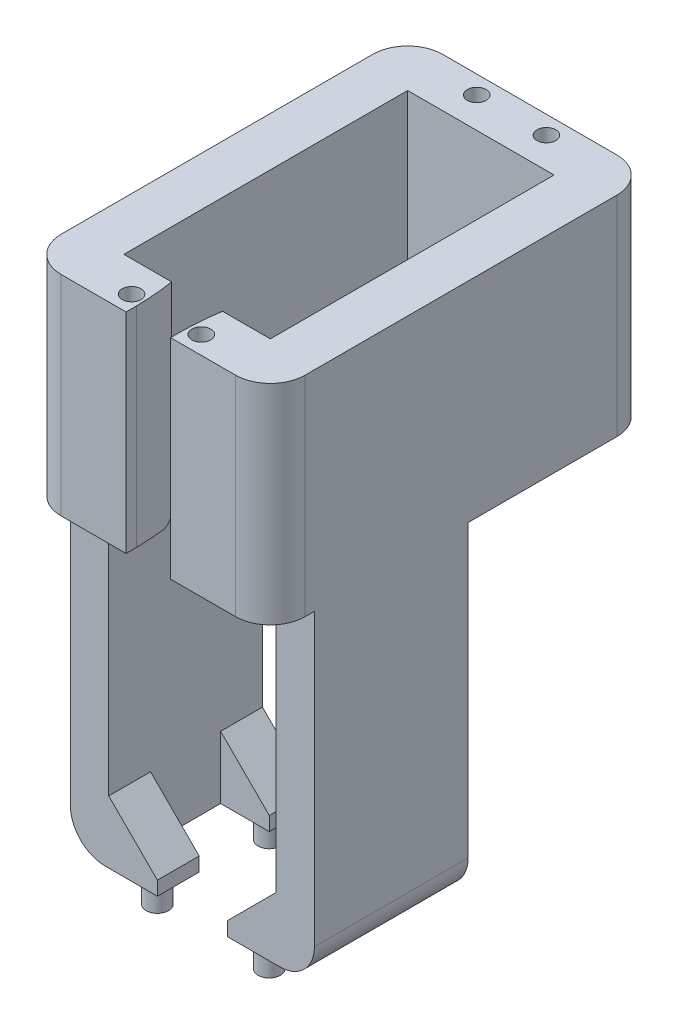
SolidWorks part; units mm, degrees
ref_plane "Front Plane" through (0, 0, 0) normal (0, 0, 1) x (1, 0, 0)
ref_plane "Top Plane" through (0, 0, 0) normal (0, 1, 0) x (1, 0, 0)
ref_plane "Right Plane" through (0, 0, 0) normal (1, 0, 0) x (0, 0, -1)
sketch "Sketch2" plane through (0, 0, 0) normal (0, 1, 0) x (1, 0, 0)
  line L0 (-17.5, 27.35) -> (-17.5, -27.35)
  line L1 (-10.5, 20.35) -> (10.5, 20.35)
  line L2 (-10.5, 20.35) -> (-10.5, -20.35)
  line L3 (-10.5, -20.35) -> (10.5, -20.35)
  line L4 (10.5, 20.35) -> (10.5, -20.35)
  line L5 (-10.5, 20.35) -> (10.5, -20.35) construction
  line L6 (-10.5, -20.35) -> (10.5, 20.35) construction
  line L7 (-17.5, -27.35) -> (17.5, -27.35)
  line L8 (17.5, 27.35) -> (17.5, -27.35)
  line L9 (-17.5, 27.35) -> (17.5, 27.35)
  line L10 (0, 20.35) -> (0, -20.35) construction
  line L11 (-10.5, 0) -> (10.5, 0) construction
  circle A0 centre (-5, 24.75) radius 1.35
  circle A1 centre (5, 24.75) radius 1.35
  circle A2 centre (-5, -24.75) radius 1.35
  circle A3 centre (5, -24.75) radius 1.35
  point P0 (0, 0)
  dimension "D7" = 2.7
  dimension "D8" = 24.75
  dimension "D9" = 5
  dimension "D1" = 21
  dimension "D2" = 40.7
  dimension "D3" = 7
  dimension "D4" = 7
  dimension "D5" = 7
  dimension "D6" = 7
extrude "Boss-Extrude1" add sketch "Sketch2" against normal blind 30
sketch "Sketch4" plane through (0, 0, 0) normal (0, 1, 0) x (1, 0, 0)
  line L0 (-3.25, -21.85) -> (-3.05, -21.85) construction
  line L1 (-10.5, -20.35) -> (10.5, -20.35) construction
  line L2 (-3.25, -20.35) -> (-3.25, -21.85) construction
  line L3 (-3, -25.85) -> (3, -25.85) construction
  line L4 (3.25, -20.35) -> (-3.25, -20.35) construction
  line L5 (-3.05, -21.85) -> (-3, -25.85) construction
  line L6 (0, -20.35) -> (0, -25.85) construction
  line L7 (3.25, -20.35) -> (3.25, -21.85) construction
  line L8 (3.25, -21.85) -> (3.05, -21.85) construction
  line L9 (3.05, -21.85) -> (3, -25.85) construction
  line L10 (-3, -25.85) -> (-2.25, -25.85) construction
  line L11 (-2.25, -25.85) -> (-2.25, -27.35) construction
  line L12 (-17.5, -27.35) -> (17.5, -27.35) construction
  line L13 (-2.25, -27.35) -> (2.25, -27.35) construction
  line L14 (2.25, -27.35) -> (2.25, -25.85) construction
  line L15 (2.25, -25.85) -> (3, -25.85) construction
  line L16 (-3.25, -21.8525) -> (-3.2, -25.8525) construction
  line L17 (-3.45, -20.35) -> (-3.45, -21.85) construction
  line L18 (-3.2, -25.8525) -> (-3.1813, -27.35)
  line L19 (-3.6478, -20.35) -> (3.6478, -20.35)
  line L20 (3.1813, -27.35) -> (-3.1813, -27.35)
  line L21 (3.2, -25.8525) -> (3.1813, -27.35)
  arc A0 (-3.2, -25.8525) -> (-3.6478, -20.35) centre (-43.4094, -26.3551) ccw
  arc A1 (3.2, -25.8525) -> (3.6478, -20.35) centre (43.4094, -26.3551) cw
  point P11 (0, -20.35)
  dimension "D1" = 6.5
  dimension "D2" = 1.5
  dimension "D3" = 6
  dimension "D4" = 4.5
  dimension "D5" = 4
  dimension "D6" = 6.1
  dimension "D7" = 0.2
extrude "Cut-Extrude2" cut sketch "Sketch4" against normal up to next
fillet "Bordes_Servo" radius 1.5 5 edges at (0, -30, -20.35) (-7.0739, -30, 20.35) (7.0739, -30, 20.35) (-10.5, -30, 0) (10.5, -30, 0)
sketch "Sketch5" plane through (0, -30, 0) normal (0, -1, 0) x (1, 0, 0)
  line L0 (-3.6478, 20.35) -> (-10.5, 20.35) construction
  line L1 (-17.5, -27.35) -> (-17.5, 27.35) construction
  line L2 (-8.025, 1.975) -> (8.025, 1.975) construction
  line L3 (-8.025, 1.975) -> (-8.025, 18.025) construction
  line L4 (-8.025, 18.025) -> (8.025, 18.025) construction
  line L5 (8.025, 1.975) -> (8.025, 18.025) construction
  line L6 (-8.025, 1.975) -> (8.025, 18.025) construction
  line L7 (-8.025, 18.025) -> (8.025, 1.975) construction
  line L12 (-17.5, 21.025) -> (-12, 21.025)
  line L13 (-17.5, 21.025) -> (-17.5, -1.025)
  line L14 (-17.5, -1.025) -> (-12, -1.025)
  line L15 (-12, 21.025) -> (-12, -1.025)
  line L16 (-12, -21.85) -> (-12, 21.85) construction
  line L17 (0, 18.025) -> (0, 1.975) construction
  line L18 (-12, 21.025) -> (-5.025, 21.025)
  line L19 (-12, 21.025) -> (-12, 15.025)
  line L20 (-12, 15.025) -> (-5.025, 15.025)
  line L21 (-5.025, 21.025) -> (-5.025, 15.025)
  line L22 (-8.025, 10) -> (8.025, 10) construction
  line L23 (-5.025, -1.025) -> (-5.025, 4.975)
  line L24 (-12, 4.975) -> (-5.025, 4.975)
  line L25 (-12, -1.025) -> (-12, 4.975)
  line L26 (-12, -1.025) -> (-5.025, -1.025)
  line L27 (8.025, 1.975) -> (8.025, 18.025) construction
  line L28 (12, -1.025) -> (5.025, -1.025)
  line L29 (12, -1.025) -> (12, 4.975)
  line L30 (12, 4.975) -> (5.025, 4.975)
  line L31 (5.025, -1.025) -> (5.025, 4.975)
  line L32 (5.025, 21.025) -> (5.025, 15.025)
  line L33 (12, 15.025) -> (5.025, 15.025)
  line L34 (12, 21.025) -> (12, 15.025)
  line L35 (12, 21.025) -> (5.025, 21.025)
  line L36 (12, 21.025) -> (12, -1.025)
  line L37 (17.5, -1.025) -> (12, -1.025)
  line L38 (17.5, 21.025) -> (17.5, -1.025)
  line L39 (17.5, 21.025) -> (12, 21.025)
  circle A0 centre (8.025, 1.975) radius 1.6
  circle A1 centre (-8.025, 1.975) radius 1.6
  circle A2 centre (-8.025, 18.025) radius 1.6
  circle A3 centre (8.025, 18.025) radius 1.6
  point P0 (0, 10)
  point P5 (0, 10)
  line M3 (-17.5, 27.35) -> (-17.5, -27.35)
  line M7 (17.5, -27.35) -> (17.5, 27.35)
  line M13 (12, 21.85) -> (12, -21.85)
  line M15 (-12, -21.85) -> (-12, 21.85)
  dimension "D4" = 3.2
  dimension "D1" = 10.35
  dimension "D2" = 10.5
  dimension "D3" = 16.05
  dimension "D5" = 3
  dimension "D7" = 3
  dimension "D8" = 3
extrude "Altura torres" add sketch "Sketch5" along normal blind 46.6566 contours L14 L15 L12 M3 M15 | L39 L37 M7 M13 region at (-14.75, -30, 10) region at (14.75, -30, 10)
extrude "Boss-Extrude3" add sketch "Sketch5<3>" against normal blind 2 from surface contours L26 L23 L24 L25 | L19 L20 L21 L18 | L34 L33 L32 L35 | L28 L31 L30 L29 starting at face at (-14.75, -76.6566, 10)
sketch "Sketch5<3>" plane through (0, -30, 0) normal (0, -1, 0) x (1, 0, 0) same geometry as "Sketch5"
chamfer "Chamfer1" distance 6.975 angle 45 4 edges at (12, -74.6566, 18.025) (12, -74.6566, 1.975) (-12, -74.6566, 18.025) (-12, -74.6566, 1.975)
extrude "Boss-Extrude4" add sketch "Sketch5<4>" along normal blind 4 from surface contours A1 | A2 | A3 | A0 starting at face at (-9.8875, -76.6566, 10)
sketch "Sketch5<4>" plane through (0, -30, 0) normal (0, -1, 0) x (1, 0, 0) same geometry as "Sketch5"
fillet "Bordes_Ext" radius 5 6 edges at (-17.5, -15, 27.35) (17.5, -15, 27.35) (-17.5, -15, -27.35) (17.5, -15, -27.35) (17.5, -76.6566, 10) (-17.5, -76.6566, 10)
